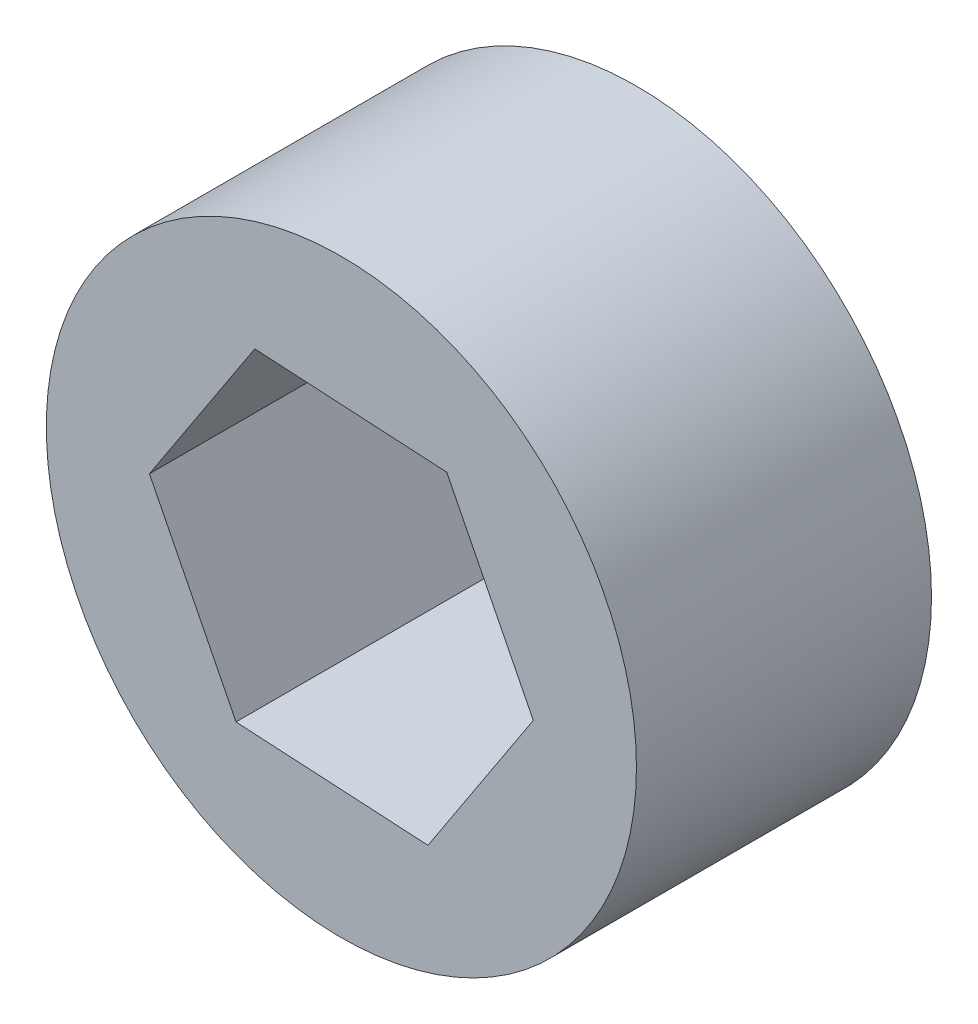
SolidWorks part; units mm, degrees
material "PET"
ref_plane "Front Plane" through (0, 0, 0) normal (0, 0, 1) x (1, 0, 0)
ref_plane "Top Plane" through (0, 0, 0) normal (0, 1, 0) x (1, 0, 0)
ref_plane "Right Plane" through (0, 0, 0) normal (1, 0, 0) x (0, 0, -1)
sketch "Sketch1" plane through (0, 0, 0) normal (0, 0, 1) x (1, 0, 0)
  line L1 (-5.0064, 0) -> (-2.3978, -5.1719)
  line L2 (-2.3978, -5.1719) -> (3.3855, -5.4988)
  line L3 (3.3855, -5.4988) -> (6.5603, -0.6538)
  line L4 (6.5603, -0.6538) -> (3.9517, 4.5182)
  line L5 (3.9517, 4.5182) -> (-1.8316, 4.8451)
  line L6 (-1.8316, 4.8451) -> (-5.0064, 0)
  circle A1 centre (0.777, -0.3269) radius 8.89
  circle A2 centre (0.777, -0.3269) radius 5.0165 construction
  point P0 (0, 0)
  dimension "D1" = 17.78
  dimension "D2" = 10.033
extrude "Boss-Extrude1" add sketch "Sketch1" along normal mid plane 8.89
